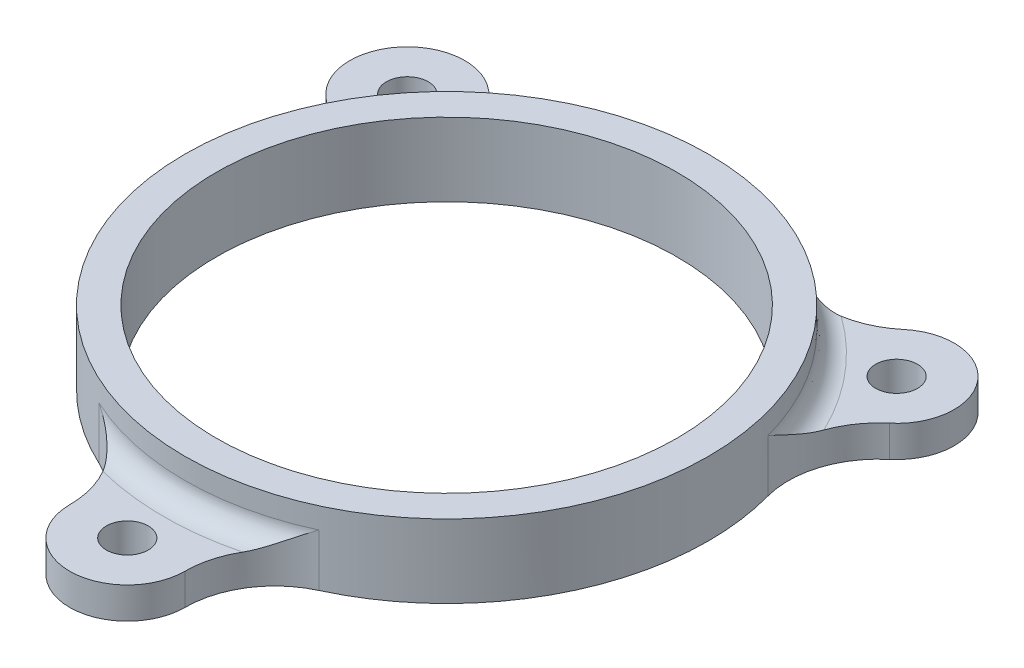
SolidWorks part; units mm, degrees
ref_plane "Front Plane" through (0, 0, 0) normal (0, 0, 1) x (1, 0, 0)
ref_plane "Top Plane" through (0, 0, 0) normal (0, 1, 0) x (1, 0, 0)
ref_plane "Right Plane" through (0, 0, 0) normal (1, 0, 0) x (0, 0, -1)
sketch "Sketch2" plane through (0, 0, 0) normal (0, 0, 1) x (1, 0, 0)
  line L0 (0, -906.0665) -> (0, 44397.2593) construction
  line L1 (-36, 0) -> (-36, -3)
  line L2 (-36, -3) -> (-22, -3)
  line L3 (-22, -3) -> (-22, 4)
  line L4 (-25, 4) -> (-25, 0)
  line L5 (-25, 0) -> (-36, 0)
  line L6 (-22, 4) -> (-25, 4)
  dimension "D4" = 36
  dimension "D5" = 3
  dimension "D2" = 22
  dimension "D1" = 3
  dimension "D3" = 7
revolve "Revolve1" add sketch "Sketch2" angle 360 about L0
sketch "Sketch3" plane through (0, -3, 0) normal (0, -1, 0) x (1, 0, 0)
  line L0 (0, 36) -> (0, 25) construction
  line L1 (0, 0) -> (-23.3644, -19.605) construction
  line L2 (0, 0) -> (23.3644, -19.605) construction
  line L3 (0, 0) -> (0, -25) construction
  circle A0 centre (0, 30.5) radius 2
  circle A3 centre (0, 0) radius 36 construction
  arc A4 (5.5, 30.5) -> (-5.5, 30.5) centre (0, 30.5) ccw
  circle A5 centre (23.3644, -19.605) radius 2
  circle A6 centre (-23.3644, -19.605) radius 2
  circle A7 centre (0, 0) radius 25 construction
  circle A8 centre (0, 0) radius 25
  arc A9 (-10.4922, 22.6917) -> (-5.5, 30.5) centre (-14.1026, 30.5) ccw
  arc A10 (10.4922, 22.6917) -> (5.5, 30.5) centre (14.1026, 30.5) cw
  arc A11 (19.829, -23.8183) -> (26.8997, -15.3918) centre (23.3644, -19.605) ccw
  arc A12 (24.1271, -6.5485) -> (26.8997, -15.3918) centre (32.4293, -8.8018) ccw
  arc A13 (10.6386, -22.6234) -> (19.829, -23.8183) centre (14.2994, -30.4082) cw
  arc A14 (-26.8997, -15.3918) -> (-19.829, -23.8183) centre (-23.3644, -19.605) ccw
  arc A15 (-10.6386, -22.6234) -> (-19.829, -23.8183) centre (-14.2994, -30.4082) ccw
  arc A16 (-24.1271, -6.5485) -> (-26.8997, -15.3918) centre (-32.4293, -8.8018) cw
  point P15 (0, 0)
  point P38 (0, 0)
  circle M5 centre (0, 0) radius 36
  dimension "D1" = 4
  dimension "D2" = 100
  dimension "D3" = 30.5
  dimension "D4" = 30.5
extrude "Cut-Extrude1" cut sketch "Sketch3" against normal through all and the other way blind 10 contours A16 A8 A9 A4 A14 M5 | A8 A12 A11 A4 A10 M5 | A8 A15 A14 A11 A13 M5 | A0 | A6 | A5 region at (23.9726, -3, 11.1786) region at (-23.9726, -3, 11.1786) region at (0, -3, -28.6142)
fillet "Fillet1" radius 2 3 edges at (0, 0, 25) (-19.1511, 0, -16.0697) (19.1511, 0, -16.0697)
equation "\"in_d\"=40"
equation "\"pipe_thick\"=2"
equation "\"D4@Sketch2\"=\"in_d\"/2+16"
equation "\"D2@Sketch2\"=\"in_d\"/2+\"pipe_thick\""
